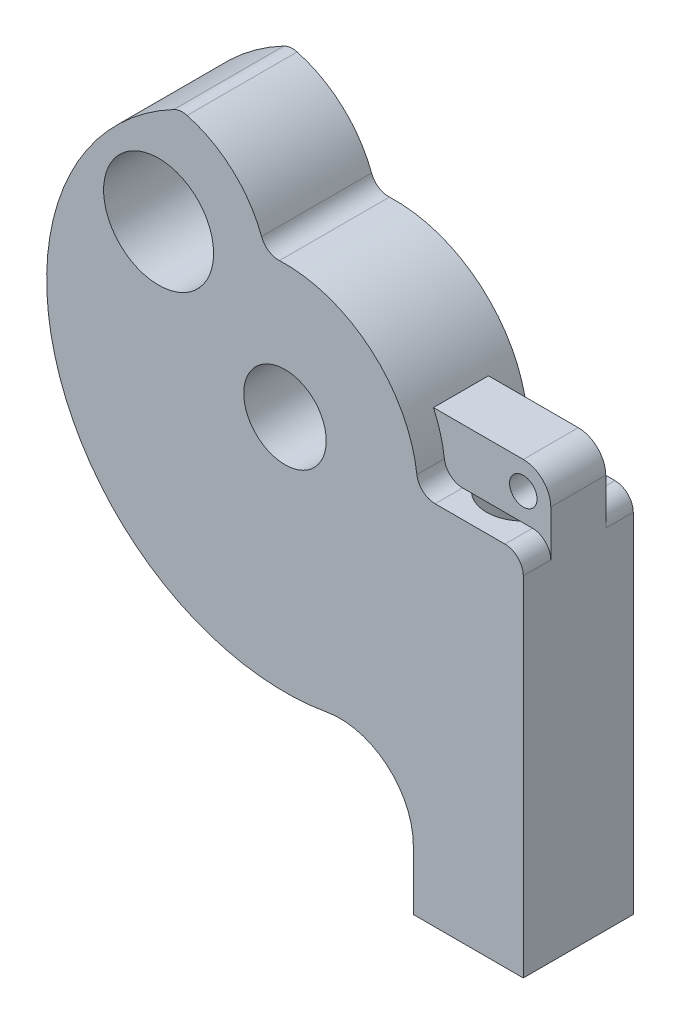
SolidWorks part; units mm, degrees
ref_plane "Front Plane" through (0, 0, 0) normal (0, 0, 1) x (1, 0, 0)
ref_plane "Top Plane" through (0, 0, 0) normal (0, 1, 0) x (1, 0, 0)
ref_plane "Right Plane" through (0, 0, 0) normal (1, 0, 0) x (0, 0, -1)
sketch "Sketch2" plane through (0, 0, 0) normal (0, 0, 1) x (1, 0, 0)
  line L0 (13, 0) -> (13, -20)
  line L1 (13, -20) -> (7, -20)
  line L2 (7, -20) -> (7, -10.9545)
  line L3 (10, 0) -> (10, -20) construction
  arc A0 (13, 0) -> (7, -10.9545) centre (0, 0) ccw
  circle A1 centre (0, 0) radius 10 construction
  dimension "Diameter" = 20
  dimension "Rod Holer Thickness" = 6
  dimension "Rod Holder Length" = 20
extrude "Boss-Extrude1" add sketch "Sketch2" along normal mid plane 6
hole_wizard "M4 Clearance Hole1" positions "Sketch3" profile "Sketch4" hole size "M4" standard "ANSI Metric" end condition up to next
sketch "Sketch3" plane through (0, 0, 3) normal (0, 0, 1) x (1, 0, 0)
  point P2 (0, 0)
sketch "Sketch4" plane through (0, 0, 3) normal (1, 0, 0) x (0, -1, 0)
  line L0 (0, 0) -> (0, 6)
  line L1 (0, 6) -> (2.25, 6)
  line L2 (2.25, 6) -> (2.25, 0)
  line L5 (2.25, 0) -> (0, 0)
  line L11 (0, -6.35) -> (0, 107.95) construction
  dimension "Thru Hole Dia." = 4.5
  dimension "Thru Hole Depth" = 6
sketch "Sketch5" plane through (0, -20, 0) normal (0, -1, 0) x (1, 0, 0)
  line L0 (13, 3) -> (7, -3) construction
  circle A0 centre (10, 0) radius 2
  dimension "Rod Hole Diameter" = 4
extrude "Cut-Extrude1" cut sketch "Sketch5" against normal blind 20
ref_axis "Axis1" through (10, 0, 0) along (0, -1, 0)
sketch "Sketch8" plane through (0, 0, 3) normal (0, 0, 1) x (1, 0, 0)
  line L0 (0, 0) -> (-21.8723, 0) construction
  line L1 (0, 0) -> (-6.8944, 5.7851) construction
  circle A0 centre (-6.8944, 5.7851) radius 3
  dimension "D2" = 6
  dimension "D1" = 40
  dimension "D3" = 9
extrude "Cut-Extrude3" cut sketch "Sketch8" against normal through all
sketch "Sketch9" plane through (0, 0, 3) normal (0, 0, 1) x (1, 0, 0)
  line L1 (13, 0) -> (7.25, 0)
  line L2 (13, 0) -> (13, 10.075) construction
  arc A0 (13, 0) -> (7, -10.9545) centre (0, 0) ccw construction
  arc A1 (7.25, 0) -> (-1.057, 7.1725) centre (0, 0) ccw
  circle A2 centre (0, 0) radius 2.25 construction
  arc A4 (-1.057, 7.1725) -> (-5.7272, 11.6705) centre (-6.8944, 5.7851) ccw
  circle A5 centre (-6.8944, 5.7851) radius 3 construction
  arc A6 (13, 0) -> (-5.7272, 11.6705) centre (0, 0) ccw
  dimension "D1" = 5
  dimension "D2" = 3
extrude "Cut-Extrude4" cut sketch "Sketch9" against normal through all
sketch "Sketch6" plane through (0, 0, 0) normal (0, 0, 1) x (1, 0, 0)
  line L4 (13, 1.5) -> (13, 0)
  line L6 (11.5, 3) -> (6.6002, 3)
  line L8 (7.25, 0) -> (13, 0) construction
  line L9 (7.25, 0) -> (13, 0)
  arc A2 (13, 1.5) -> (11.5, 3) centre (11.5, 1.5) ccw
  arc A3 (7.25, 0) -> (-1.057, 7.1725) centre (0, 0) ccw construction
  arc A4 (7.25, 0) -> (6.6002, 3) centre (0, 0) ccw
  dimension "Spring Attchment Diameter" = 1.5
extrude "Boss-Extrude2" add sketch "Sketch6" along normal mid plane 3
fillet "Fillet1" radius 1 6 edges at (-5.7272, 11.6705, 0) (7.25, 0, 2.25) (7.25, 0, -2.25) (-1.057, 7.1725, 0) (13, 0, -2.25) (13, 0, 2.25)
sketch "Sketch7" plane through (0, 0, 1.5) normal (0, 0, 1) x (1, 0, 0)
  circle A0 centre (11.5, 1.5) radius 0.75
  arc A1 (13, 1.5) -> (11.5, 3) centre (11.5, 1.5) ccw construction
  dimension "Spring Hole Diam" = 1.5
extrude "Cut-Extrude2" cut sketch "Sketch7" against normal through all both and the other way through all
fillet "Fillet2" radius 4 1 edges at (7, -10.9545, 0)
